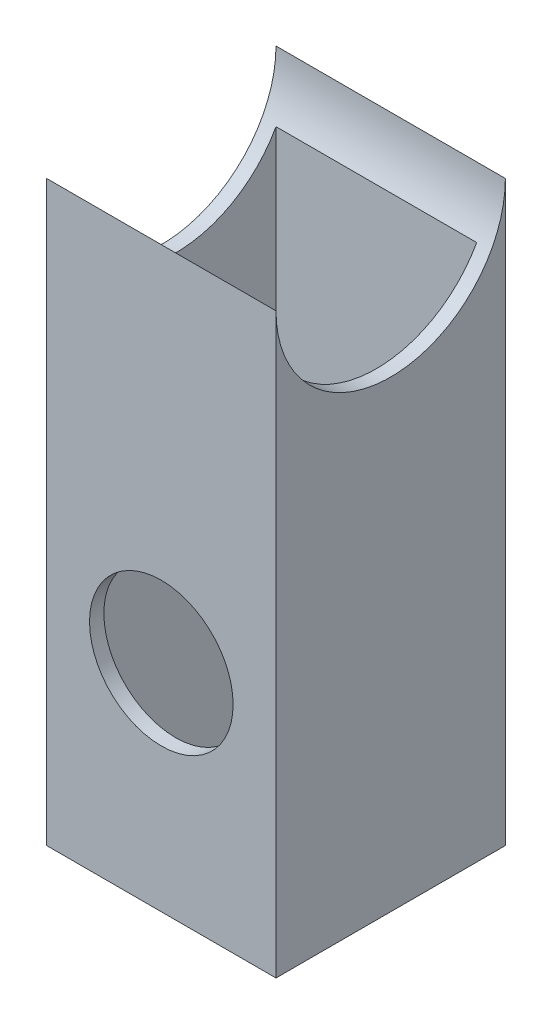
SolidWorks part; units mm, degrees
ref_plane "Front Plane" through (0, 0, 0) normal (0, 0, 1) x (1, 0, 0)
ref_plane "Top Plane" through (0, 0, 0) normal (0, 1, 0) x (1, 0, 0)
ref_plane "Right Plane" through (0, 0, 0) normal (1, 0, 0) x (0, 0, -1)
sketch "Sketch1" plane through (0, 0, 0) normal (0, 1, 0) x (1, 0, 0)
  line L0 (11.1125, 11.1125) -> (-11.1125, 11.1125)
  line L1 (12.7, 12.7) -> (-12.7, 12.7)
  line L2 (-12.7, 12.7) -> (-12.7, -12.7)
  line L3 (-12.7, -12.7) -> (12.7, -12.7)
  line L4 (12.7, -12.7) -> (12.7, 12.7)
  line L5 (-11.1125, 11.1125) -> (-11.1125, -11.1125)
  line L6 (-11.1125, -11.1125) -> (11.1125, -11.1125)
  line L7 (11.1125, -11.1125) -> (11.1125, 11.1125)
  circle A0 centre (0, 0) radius 12.7 construction
  dimension "D1" = 25.4
  dimension "D2" = 1.5875
extrude "Boss-Extrude1" add sketch "Sketch1" along normal blind 63.9826
sketch "Sketch2" plane through (0, 0, 12.7) normal (0, 0, 1) x (1, 0, 0)
  line L2 (0, 23.8506) -> (0, 0) construction
  line L3 (12.7, 63.9826) -> (12.7, 0) construction
  circle A0 centre (0, 23.8506) radius 7.9502
  dimension "D1" = 15.9004
  dimension "D2" = 23.8506
extrude "Cut-Extrude1" cut sketch "Sketch2" against normal through all both and the other way through all
sketch "Sketch3" plane through (12.7, 0, 0) normal (1, 0, 0) x (0, 0, -1)
  line L0 (-12.7, 63.9826) -> (12.7, 63.9826) construction
  circle A0 centre (0, 63.9826) radius 12.7
  dimension "D1" = 25.4
extrude "Cut-Extrude2" cut sketch "Sketch3" against normal through all
equation "\"diameter\"= .626in"
equation "\"D1@Sketch2\"= \"diameter\""
equation "\"D2@Sketch2\"=1.5*\"diameter\""
equation "\"bolt_diam\"= .1160in"
equation "\"padding\"= .15in"
equation "\"D1@Boss-Extrude1\"=2.519"
